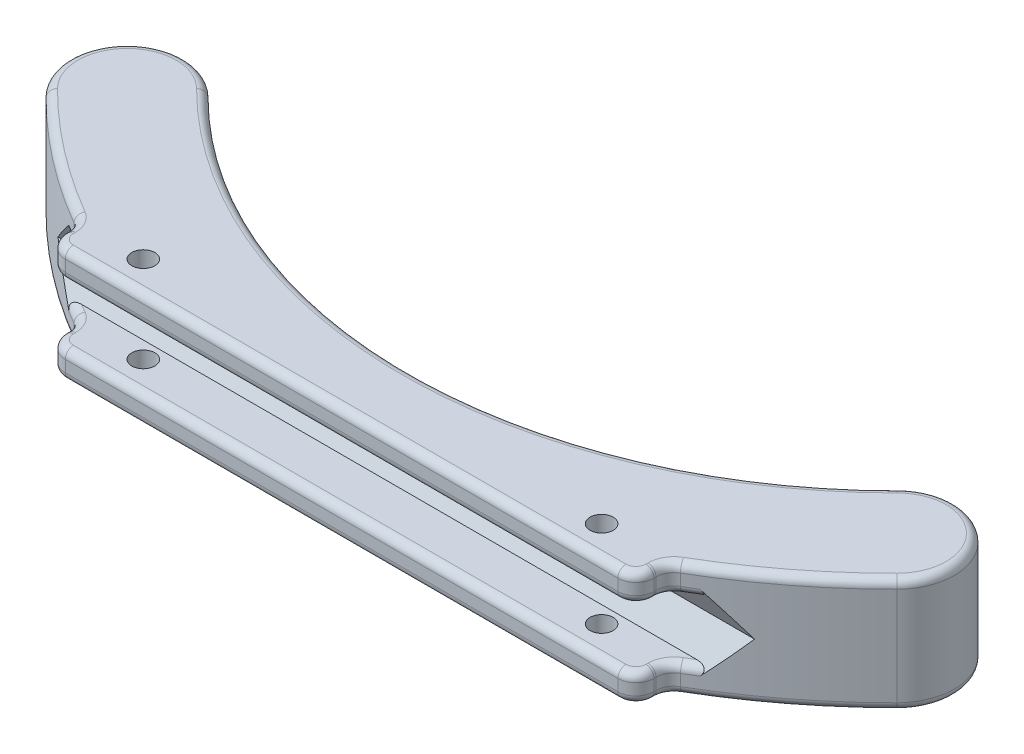
SolidWorks part; units mm, degrees
material "PET"
ref_plane "Front Plane" through (0, 0, 0) normal (0, 0, 1) x (1, 0, 0)
ref_plane "Top Plane" through (0, 0, 0) normal (0, 1, 0) x (1, 0, 0)
ref_plane "Right Plane" through (0, 0, 0) normal (1, 0, 0) x (0, 0, -1)
sketch "Sketch1" plane through (0, 0, 0) normal (0, 1, 0) x (1, 0, 0)
  line L5 (-65.2552, 0) -> (65.2552, 0) construction
  line L8 (76.3675, 39.9825) -> (94.328, 22.022) construction
  line L9 (-94.328, 22.022) -> (-76.3675, 39.9825) construction
  line L10 (0, 116.35) -> (0, 0) construction
  line L11 (-65.2552, 0) -> (-65.2552, -3.78)
  line L12 (-65.2552, -3.78) -> (65.2552, -3.78)
  line L13 (65.2552, -3.78) -> (65.2552, 0)
  arc A0 (76.3675, 39.9825) -> (-76.3675, 39.9825) centre (0, 116.35) cw
  arc A1 (94.328, 22.022) -> (65.2552, 0) centre (0, 116.35) cw
  arc A2 (-94.328, 22.022) -> (-76.3675, 39.9825) centre (-85.3478, 31.0022) cw
  arc A3 (76.3675, 39.9825) -> (94.328, 22.022) centre (85.3478, 31.0022) cw
  arc A4 (-65.2552, 0) -> (-94.328, 22.022) centre (0, 116.35) cw
  arc A5 (94.328, 22.022) -> (-94.328, 22.022) centre (0, 116.35) cw construction
  dimension "D1" = 108
  dimension "D3" = 90
  dimension "D4" = 3.78
  dimension "D8" = 116.35
  dimension "D2" = 25.4
extrude "Boss-Extrude1" add sketch "Sketch1" along normal mid plane 25.4
sketch "Sketch3" plane through (0, 0, 0) normal (1, 0, 0) x (0, 0, -1)
  line L1 (-7.5633, 0) -> (-3.7816, -6.55)
  line L2 (-3.7816, -6.55) -> (3.7816, -6.55)
  line L3 (3.7816, -6.55) -> (7.5633, 0)
  line L4 (7.5633, 0) -> (3.7816, 6.55)
  line L5 (3.7816, 6.55) -> (-3.7816, 6.55)
  line L6 (-3.7816, 6.55) -> (-7.5633, 0)
  circle A0 centre (0, 0) radius 6.55 construction
  dimension "D1" = 13.1
extrude "Cut-Extrude1" cut sketch "Sketch3" against normal through all both and the other way through all
hole_wizard "#10 Clearance Hole2" positions "Sketch6" profile "Sketch7" hole size "#10" standard "ANSI Inch" end condition through all
sketch "Sketch6" plane through (0, 12.7, 0) normal (0, 1, 0) x (1, 0, 0)
  line L8 (-65.2552, 0) -> (-65.2552, -3.78)
  line L10 (65.2552, -3.78) -> (65.2552, 0)
  line L11 (71.5816, 3.7816) -> (-71.5816, 3.7816)
  line L12 (-65.2552, 0) -> (-65.2552, -3.78) construction
  line L14 (65.2552, -3.78) -> (65.2552, 0) construction
  line L15 (71.5816, 3.7816) -> (-71.5816, 3.7816) construction
  line L16 (0, 3.7816) -> (0, -3.65) construction
  line L56 (-65.2552, -3.78) -> (65.2552, -3.78)
  line L57 (-65.2552, -3.78) -> (65.2552, -3.78)
  arc A4 (65.2552, 0) -> (71.5816, 3.7816) centre (0, 116.35) ccw
  arc A5 (-71.5816, 3.7816) -> (-65.2552, 0) centre (0, 116.35) ccw
  arc A6 (65.2552, 0) -> (71.5816, 3.7816) centre (0, 116.35) ccw construction
  arc A7 (-71.5816, 3.7816) -> (-65.2552, 0) centre (0, 116.35) ccw construction
  point P0 (-50.8, 0.0658)
  point P2 (50.8, 0.0658)
  point P39 (0, 0.0658)
  dimension "D2" = 101.6
  dimension "D1" = 0
sketch "Sketch7" plane through (-50.8, 12.7, -0.0658) normal (1, 0, 0) x (0, 0, 1)
  line L0 (0, 0) -> (0, 25.4)
  line L1 (0, 25.4) -> (2.5527, 25.4)
  line L2 (2.5527, 25.4) -> (2.5527, 0)
  line L5 (2.5527, 0) -> (0, 0)
  line L11 (0, -6.35) -> (0, 107.95) construction
  dimension "Thru Hole Dia." = 5.1054
  dimension "Thru Hole Depth" = 25.4
sketch "Sketch8" plane through (0, 0, 3.78) normal (0, 0, 1) x (1, 0, 0)
  line L0 (65.2552, -12.7) -> (65.2552, -6.55) construction
  line L1 (65.2552, -6.55) -> (-65.2552, -6.55) construction
  line L2 (-65.2552, -6.55) -> (-65.2552, -12.7) construction
  line L3 (-65.2552, -12.7) -> (65.2552, -12.7) construction
  line L4 (-65.2552, 12.7) -> (-65.2552, 6.55) construction
  line L5 (-65.2552, 6.55) -> (65.2552, 6.55) construction
  line L6 (65.2552, 6.55) -> (65.2552, 12.7) construction
  line L7 (65.2552, 12.7) -> (-65.2552, 12.7) construction
  line L8 (65.2552, -12.7) -> (65.2552, -6.55)
  line L9 (65.2552, -6.55) -> (-65.2552, -6.55)
  line L10 (-65.2552, -6.55) -> (-65.2552, -12.7)
  line L11 (-65.2552, -12.7) -> (65.2552, -12.7)
  line L12 (-65.2552, 12.7) -> (-65.2552, 6.55)
  line L13 (-65.2552, 6.55) -> (65.2552, 6.55)
  line L14 (65.2552, 6.55) -> (65.2552, 12.7)
  line L15 (65.2552, 12.7) -> (-65.2552, 12.7)
extrude "Boss-Extrude2" add sketch "Sketch8" along normal blind 3
fillet "Fillet1" radius 4 8 edges at (-65.2552, -9.625, 6.78) (-65.2552, 9.625, 6.78) (65.2552, 9.625, 6.78) (65.2552, -9.625, 6.78) (65.2552, -9.625, 0) (65.2552, 9.625, 0) (-65.2552, -9.625, 0) (-65.2552, 9.625, 0)
fillet "Fillet2" radius 1.8 42 edges at (69.4229, -6.55, -2.4377) (65.7864, -6.55, 0.3277) (65.2552, -6.55, 2.5498) (64.0836, -6.55, 5.6084) (-69.4229, -6.55, -2.4377) (-65.7864, -6.55, 0.3277) (-65.2552, -6.55, 2.5498) (-64.0836, -6.55, 5.6084) (69.4229, 6.55, -2.4377) (65.7864, 6.55, 0.3277) (65.2552, 6.55, 2.5498) (-69.4229, 6.55, -2.4377) (-65.7864, 6.55, 0.3277) (-65.2552, 6.55, 2.5498) (-64.0836, 6.55, 5.6084) (0, 6.55, 6.78) (65.7864, -12.7, 0.3277) (65.2552, -12.7, 2.5498) (64.0836, -12.7, 5.6084) (0, -12.7, 6.78) (-64.0836, -12.7, 5.6084) (-65.2552, -12.7, 2.5498) (-65.7864, -12.7, 0.3277) (-81.4558, -12.7, -10.7067) (-94.328, -12.7, -39.9825) (0, -12.7, -8.35) (94.328, -12.7, -39.9825) (-94.328, 12.7, -39.9825) (0, 12.7, -8.35) (94.328, 12.7, -39.9825) (81.4558, 12.7, -10.7067) (65.7864, 12.7, 0.3277) (65.2552, 12.7, 2.5498) (64.0836, 12.7, 5.6084) (0, 12.7, 6.78) (-64.0836, 12.7, 5.6084) (-65.2552, 12.7, 2.5498) (-65.7864, 12.7, 0.3277) (0, -6.55, 6.78) (64.0836, 6.55, 5.6084) (81.4558, -12.7, -10.7067) (-81.4558, 12.7, -10.7067)
